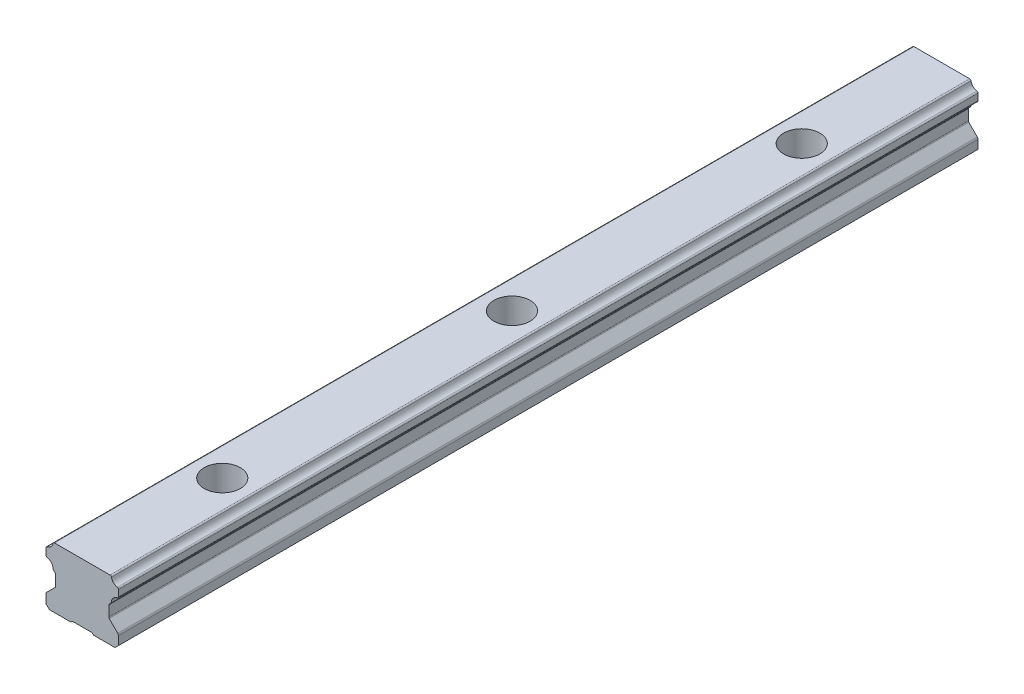
SolidWorks part; units mm, degrees
note: '?' marks a value the reader was unsure of.
ref_plane "Front Plane" through (0, 0, 0) normal (0, 0, 1) x (1, 0, 0)
ref_plane "Top Plane" through (0, 0, 0) normal (0, 1, 0) x (1, 0, 0)
ref_plane "Right Plane" through (0, 0, 0) normal (1, 0, 0) x (0, 0, -1)
ref_axis "Axis_X" through (-8.25, 0, 0) along (1, 0, 0)?
ref_axis "Axis_Y" through (0, 13.125, 0) along (0, -1, 0)?
ref_axis "Axis_Z" through (0, 0, -101.5) along (0, 0, 1)?
ref_plane "Plane1" through (0, 0, 29) normal (0, 0, 1) x (1, 0, 0)
sketch "Sketch1" plane through (0, 0, 29) normal (0, 0, 1) x (1, 0, 0)
  line L0 (-2.05, 0.3) -> (0, 0.3)
  line L1 (0, 0) -> (0, 12.5) construction
  line L2 (-2.05, 0.3) -> (-2.35, 0)
  line L3 (-2.35, 0) -> (-7.5, 0)
  line L5 (-7.5, 0) -> (-7.5, 2.7)
  line L6 (-7.5, 2.7) -> (-5.5, 4.7)
  line L7 (-5.5, 4.7) -> (-5.5, 7.1)
  line L8 (-5.5, 7.1) -> (-7.5, 7.1)
  line L9 (0, 12.5) -> (0, 0.3)
  line L14 (-7.5, 12.5) -> (-7.5, 7.1)
  line L29 (-7.5, 12.5) -> (0, 12.5)
  dimension "KSS_1" = 0.3
  dimension "MSM_3" = 2.7
  dimension "FIX_1" = 45
  dimension "MSM_4" = 7.1
  dimension "MSM_2" = 4.1
  dimension "WR" = 15
  dimension "HR" = 12.5
  dimension "MSM_1" = 11
extrude "Boss-Extrude101" add sketch "Sketch1" against normal blind 178
sketch "Sketch2" plane through (0, 0, 29) normal (0, 0, 1) x (1, 0, 0)
  line L0 (0, 0) -> (0, 12.5) construction
  line L1 (-7.5, 0) -> (-2.35, 0) construction
  line L2 (-5.5, 7.1) -> (-6.0305, 7.6305)
  line L3 (-5.5, 4.7) -> (-7.5, 2.7) construction
  line L4 (-5.5, 7.1) -> (-5.5, 4.7)
  line L5 (-5.5, 4.7) -> (-7.5, 2.7)
  line L6 (-7.5, 2.7) -> (-7.53, 6.17)
  circle A0 centre (-7.53, 12.53) radius 1.5
  arc A1 (-6.0305, 7.6305) -> (-7.53, 6.17) centre (-7.53, 7.67) ccw
  dimension "MSM_5" = 3
  dimension "MSM_6" = 15.06
  dimension "MSM_7" = 4.86
  dimension "MSM_8" = 7.67
extrude "Cut-Extrude101" cut sketch "Sketch2" against normal through all
chamfer "Chamfer101" distance 0.7 1 edges at (-7.5, 0, -60)
fillet "Fillet101" radius 0.5 1 edges at (-7.5, 2.7, -60)
fillet "Fillet102" radius 0.3 1 edges at (-5.5, 7.1, -60)
fillet "Fillet103" radius 0.3 3 edges at (-7.5, 9.1697, -60) (-7.5, 11.0303, -60) (-6.0303, 12.5, -60)
fillet "Fillet104" radius 0.3 1 edges at (-5.5, 4.7, -60)
mirror "Mirror101" about plane through (0, 0, 0) normal (1, 0, 0) of "Fillet104", "Fillet103", "Fillet102", "Fillet101", "Chamfer101", "Cut-Extrude101", "Boss-Extrude101"
hole_wizard "CBORE101" positions "Sketch4" profile "Sketch3" counterbore size "M5" standard "JIS" end condition through all
sketch "Sketch4" plane through (0, 12.5, 0) normal (0, 1, 0) x (1, 0, 0)
  point P0 (0, 0)
sketch "Sketch3" plane through (0, 12.5, 0) normal (1, 0, 0) x (0, 0, 1)
  line L0 (0, 0) -> (0, 12.5)
  line L1 (0, 12.5) -> (2.25, 12.5)
  line L3 (2.25, 12.5) -> (2.25, 5.3)
  line L4 (2.25, 5.3) -> (3.75, 5.3)
  line L5 (3.75, 5.3) -> (3.75, 0)
  line L7 (3.75, 0) -> (0, 0)
  line L11 (0, -6.35) -> (0, 107.95) construction
  dimension "D_s" = 4.5
  dimension "Thru Hole Depth" = 12.5
  dimension "D" = 7.5
  dimension "H_s" = 5.3
pattern_linear "LPattern101" count 3 spacing 60 along (0, 0, -1) of "CBORE101"
hole_wizard "CBORE102" [suppressed] positions "Sketch6" profile "Sketch5" counterbore size "M5" standard "JIS"
sketch "Sketch6" [suppressed] plane through (0, 12.5, 0) normal (0, 1, 0) x (1, 0, 0)
  line L0 (5.7605, -20) -> (-5.7605, -20) construction
  point P0 (0, -19)
  dimension "ES" = 2
sketch "Sketch5" [suppressed] plane through (0, 12.5, 19) normal (1, 0, 0) x (0, 0, 1)
  line L0 (0, 0) -> (0, 12.5)
  line L1 (0, 12.5) -> (2.25, 12.5)
  line L3 (2.25, 12.5) -> (2.25, 5.3)
  line L4 (2.25, 5.3) -> (3.75, 5.3)
  line L5 (3.75, 5.3) -> (3.75, 0)
  line L7 (3.75, 0) -> (0, 0)
  line L11 (0, -6.35) -> (0, 107.95) construction
  dimension "D_s" = 4.5
  dimension "Thru Hole Depth" = 12.5
  dimension "D" = 7.5
  dimension "H_s" = 5.3
pattern_linear "LPattern102" [suppressed]
hole_wizard "CBORE103" [suppressed] positions "Sketch8" profile "Sketch7" counterbore size "M5" standard "JIS"
sketch "Sketch8" [suppressed] plane through (0, 12.5, 0) normal (0, 1, 0) x (1, 0, 0)
  line L0 (5.7605, 80) -> (-5.7605, 80) construction
  point P0 (0, 79)
  dimension "EB" = 2
sketch "Sketch7" [suppressed] plane through (0, 12.5, -79) normal (1, 0, 0) x (0, 0, 1)
  line L0 (0, 0) -> (0, 12.5)
  line L1 (0, 12.5) -> (2.25, 12.5)
  line L3 (2.25, 12.5) -> (2.25, 5.3)
  line L4 (2.25, 5.3) -> (3.75, 5.3)
  line L5 (3.75, 5.3) -> (3.75, 0)
  line L7 (3.75, 0) -> (0, 0)
  line L11 (0, -6.35) -> (0, 107.95) construction
  dimension "D_s" = 4.5
  dimension "Thru Hole Depth" = 12.5
  dimension "D" = 7.5
  dimension "H_s" = 5.3
pattern_linear "LPattern103" [suppressed]
equation "\"Factor\"= 1.082532"
equation "\"L\"=178"
equation "\"M_2\"=3"
equation "\"P\"=60"
equation "\"E@Plane1\" = ( \"L\" - ( ( \"M_2\" - 1 ) * \"P\" ) ) / 2"
equation "\"KSS_1@Sketch1\"= if ( \"WR@Sketch1\" = 15 , 0.3 , 0.5 )"
equation "\"KSS_2@Fillet101\"= if ( \"WR@Sketch1\" = 15 , 0.5 , 1.5 )"
equation "\"ES\"= 2"
equation "\"EB\"= 2"
equation "\"ES@Sketch6\"= iif ( \"ES\" > 2 * \"E@Plane1\" , 2 * \"E@Plane1\" , \"ES\" )"
equation "\"EB@Sketch8\"= iif ( \"EB\" > 2 * \"E@Plane1\" , 2 * \"E@Plane1\" , \"EB\" )"
